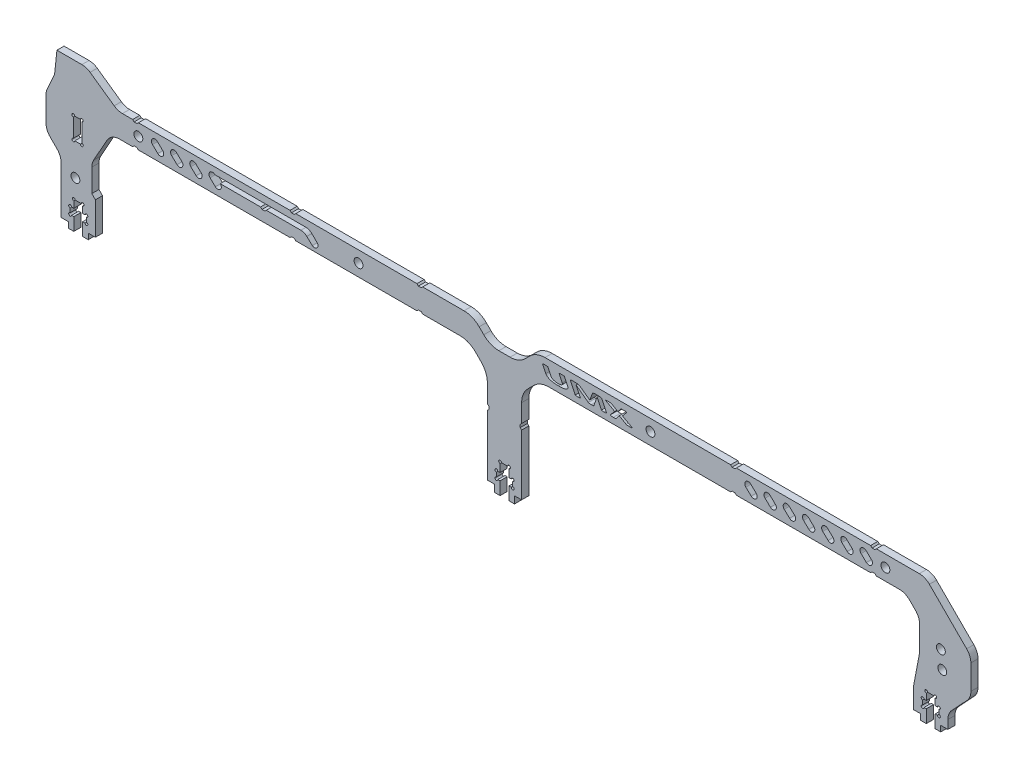
SolidWorks part; units mm, degrees
material "PPS"
ref_plane "前视基准面" through (0, 0, 0) normal (0, 0, 1) x (1, 0, 0)
ref_plane "上视基准面" through (0, 0, 0) normal (0, 1, 0) x (1, 0, 0)
ref_plane "右视基准面" through (0, 0, 0) normal (1, 0, 0) x (0, 0, -1)
sketch "草图1" plane through (0, 0, 0) normal (0, 0, 1) x (1, 0, 0)
  line L0 (-1000, 0) -> (49000, 0) construction
  line L1 (0, 0) -> (0, -218.3822) construction
  line L2 (6, -16.1697) -> (6, -48.75)
  line L3 (6, -48.75) -> (-6, -48.75) construction
  line L4 (-6, -16.1697) -> (-6, -48.75)
  line L5 (6, -48.75) -> (3.5, -48.75)
  line L6 (3.5, -48.75) -> (3.5, -51.25)
  line L7 (3.5, -51.25) -> (-3.5, -51.25) construction
  line L8 (-3.5, -48.75) -> (-3.5, -51.25)
  line L9 (-3.5, -48.75) -> (-6, -48.75)
  line L10 (1.55, -51.25) -> (1.55, -46.75)
  line L11 (1.55, -46.75) -> (2.85, -46.75)
  line L12 (2.85, -46.75) -> (2.85, -44.25)
  line L13 (2.85, -44.25) -> (1.55, -44.25)
  line L14 (1.55, -44.25) -> (1.55, -41)
  line L15 (1.55, -41) -> (-1.55, -41)
  line L16 (-1.55, -44.25) -> (-1.55, -41)
  line L17 (-2.85, -44.25) -> (-1.55, -44.25)
  line L18 (-2.85, -46.75) -> (-2.85, -44.25)
  line L19 (-1.55, -46.75) -> (-2.85, -46.75)
  line L20 (-1.55, -51.25) -> (-1.55, -46.75)
  line L21 (1.55, -51.25) -> (3.5, -51.25)
  line L22 (-1.55, -51.25) -> (-3.5, -51.25)
  line L23 (12.4197, -9.75) -> (6, -16.1697)
  line L24 (-12.4197, -9.75) -> (-6, -16.1697)
  line L25 (-147.7, -45.75) -> (-147.7, -41.25)
  line L26 (-150.8, -45.75) -> (-150.8, -41.25)
  line L27 (-147.7, -41.25) -> (-146.4, -41.25)
  line L28 (-146.4, -41.25) -> (-146.4, -38.75)
  line L29 (-146.4, -38.75) -> (-147.7, -38.75)
  line L30 (-147.7, -38.75) -> (-147.7, -36)
  line L31 (-150.8, -36) -> (-147.7, -36)
  line L32 (-150.8, -38.75) -> (-150.8, -36)
  line L33 (-152.1, -38.75) -> (-150.8, -38.75)
  line L34 (-152.1, -41.25) -> (-152.1, -38.75)
  line L35 (-150.8, -41.25) -> (-152.1, -41.25)
  line L36 (-5.0685, -7.5) -> (5.0685, -7.5)
  line L37 (5.0685, -7.5) -> (11.0685, -1.5)
  line L38 (11.0685, -1.5) -> (147.3211, -1.5)
  line L40 (145.3337, -25.5065) -> (145.3337, -14.709)
  line L41 (140.3747, -9.75) -> (12.4197, -9.75)
  line L42 (-5.0685, -7.5) -> (-11.0685, -1.5)
  line L44 (-11.0685, -1.5) -> (-157.5351, -1.5) construction
  line L45 (-137.7768, -9.75) -> (-12.4197, -9.75)
  line L50 (143.25, -36.4306) -> (143.25, -43.75)
  line L52 (155.25, -43.75) -> (143.25, -43.75) construction
  line L53 (155.25, -43.75) -> (152.75, -43.75)
  line L54 (152.75, -43.75) -> (152.75, -45.75)
  line L55 (152.75, -45.75) -> (145.75, -45.75) construction
  line L56 (145.75, -43.75) -> (145.75, -45.75)
  line L57 (145.75, -43.75) -> (143.25, -43.75)
  line L58 (150.8, -45.75) -> (150.8, -41.25)
  line L59 (150.8, -41.25) -> (152.1, -41.25)
  line L60 (152.1, -41.25) -> (152.1, -38.75)
  line L61 (152.1, -38.75) -> (150.8, -38.75)
  line L62 (150.8, -38.75) -> (150.8, -36)
  line L63 (150.8, -36) -> (147.7, -36)
  line L64 (147.7, -38.75) -> (147.7, -36)
  line L65 (146.4, -38.75) -> (147.7, -38.75)
  line L66 (146.4, -41.25) -> (146.4, -38.75)
  line L67 (147.7, -41.25) -> (146.4, -41.25)
  line L68 (147.7, -45.75) -> (147.7, -41.25)
  line L69 (150.8, -45.75) -> (152.75, -45.75)
  line L70 (147.7, -45.75) -> (145.75, -45.75)
  line L73 (145.3337, -25.5065) -> (143.25, -36.4306)
  line L74 (-147.7, -45.75) -> (-145.75, -45.75)
  line L75 (-150.8, -45.75) -> (-152.75, -45.75)
  line L76 (-152.75, -43.75) -> (-152.75, -45.75)
  line L77 (-155.25, -43.75) -> (-152.75, -43.75)
  line L78 (-145.75, -43.75) -> (-145.75, -45.75)
  line L79 (-145.75, -43.75) -> (-143.25, -43.75)
  line L80 (-157.5351, -1.5) -> (-160.547, -8.1912)
  line L81 (-160.547, -8.1912) -> (-160.547, -19.809)
  line L82 (-160.547, -19.809) -> (-155.25, -25.0873)
  line L87 (-143.25, -32.3726) -> (-144.5, -31.127)
  line L88 (-144.5, -31.127) -> (-144.5, -21.7902)
  line L89 (-144.5, -21.7902) -> (-137.7768, -9.75)
  line L90 (-155.25, -25.0873) -> (-155.25, -43.75)
  line L91 (-143.25, -32.3726) -> (-143.25, -43.75)
  line L92 (147.3211, -1.5) -> (163.2977, -17.4767)
  line L93 (163.2977, -17.4767) -> (163.2977, -30.1638)
  line L94 (163.2977, -30.1638) -> (155.25, -38.75)
  line L95 (155.25, -38.75) -> (155.25, -43.75)
  line L96 (-157.5351, -1.5) -> (-156.7241, 6.25)
  line L97 (-156.7241, 6.25) -> (-146.4, 6.25)
  line L98 (-146.4, 6.25) -> (-135.37, -1.5)
  line L99 (-135.37, -1.5) -> (-11.0685, -1.5)
  line L100 (44.6221, -11.255) -> (57.6009, -11.255) construction
  line L102 (140.3747, -9.75) -> (145.3337, -14.709)
  line L103 (44.6221, -1.505) -> (57.6009, -1.505) construction
  line L104 (146.1658, -18.25) -> (92.972, -18.25) construction
  line L105 (-154.7028, -11.25) -> (-130.7962, -11.25) construction
  circle A0 centre (-51.1115, -5.5) radius 1.55
  circle A1 centre (51.1115, -5.5) radius 1.55
  circle A2 centre (-51.1115, -5.5) radius 1.55 construction
  circle A7 centre (51.1115, -5.5) radius 1.55 construction
  point P6 (0, -48.75)
  point P11 (0, -51.25)
  point P20 (0, -41)
  point P29 (-149.25, -36)
  point P43 (152.75, -44.75)
  point P78 (149.25, -36)
  point P98 (0, 0)
  point P108 (0, 0)
  dimension "D21" = 3.1
  dimension "D1" = 3.5
  dimension "D2" = 4.5
  dimension "D3" = 2.5
  dimension "D4" = 6
  dimension "D5" = 135
  dimension "D6" = 2.5
  dimension "D7" = 48.75
  dimension "D8" = 25.5
  dimension "D9" = 2
  dimension "D10" = 7
  dimension "D11" = 149.25
  dimension "D12" = 1.95
  dimension "D13" = 1.55
  dimension "D14" = 2.85
  dimension "D15" = 10.25
  dimension "D16" = 1.505
  dimension "D17" = 2.25
  dimension "D18" = 135
  dimension "D19" = 135
  dimension "D20" = 1.25
  dimension "D22" = 17.5
  dimension "D23" = 0.005
extrude "凸台-拉伸1" add sketch "草图1" along normal blind 2.5
sketch "草图2" plane through (0, 0, 0) normal (0, 0, 1) x (1, 0, 0)
  line L0 (98.8244, -4.7341) -> (98.8244, -1.5) construction
  line L2 (147.3211, -1.5) -> (11.0685, -1.5) construction
  line L4 (100.6889, -6.5159) -> (100.6889, -9.75) construction
  line L7 (12.4197, -9.75) -> (140.3747, -9.75) construction
  line L8 (94.8107, -5.6378) -> (97.9607, -5.6378) construction
  line L11 (86.3905, -7.4197) -> (84.526, -5.6378)
  line L16 (121.7047, -5.6122) -> (124.8547, -5.6122) construction
  line L17 (106.5671, -7.394) -> (104.7026, -5.6122)
  line L18 (104.7026, -5.6122) -> (106.4054, -3.8303) construction
  line L19 (106.4054, -3.8303) -> (108.27, -5.6122)
  line L20 (108.27, -5.6122) -> (106.5671, -7.394) construction
  line L21 (99.8252, -7.4197) -> (97.9607, -5.6378)
  line L22 (99.6881, -3.8303) -> (101.5526, -5.6122)
  line L23 (101.5526, -5.6122) -> (104.7026, -5.6122) construction
  line L24 (108.27, -5.6122) -> (111.42, -5.6122) construction
  line L25 (113.2845, -7.394) -> (111.42, -5.6122)
  line L26 (113.1228, -3.8303) -> (114.9873, -5.6122)
  line L27 (114.9873, -5.6122) -> (118.1373, -5.6122) construction
  line L28 (120.0018, -7.394) -> (118.1373, -5.6122)
  line L29 (119.8402, -3.8303) -> (121.7047, -5.6122)
  line L30 (126.7192, -7.394) -> (124.8547, -5.6122)
  line L31 (126.5819, -3.8048) -> (128.4464, -5.5866)
  line L32 (86.2289, -3.856) -> (88.0934, -5.6378)
  line L33 (88.0934, -5.6378) -> (91.2434, -5.6378) construction
  line L34 (93.1079, -7.4197) -> (91.2434, -5.6378)
  line L35 (92.9462, -3.856) -> (94.8107, -5.6378)
  line L36 (-106.2679, -5.6378) -> (-103.1179, -5.6378) construction
  line L38 (-112.9852, -5.6378) -> (-109.8352, -5.6378) construction
  line L39 (-121.4054, -7.4197) -> (-123.27, -5.6378)
  line L42 (-107.9707, -7.4197) -> (-109.8352, -5.6378)
  line L44 (-108.1324, -3.856) -> (-106.2679, -5.6378)
  line L47 (-101.2387, -7.4197) -> (-103.1032, -5.6378)
  line L48 (-101.4003, -3.856) -> (-99.5358, -5.6378) construction
  line L51 (-101.4003, -3.856) -> (-69.6149, -3.856)
  line L56 (-121.5671, -3.856) -> (-119.7026, -5.6378)
  line L57 (-119.7026, -5.6378) -> (-116.5526, -5.6378) construction
  line L58 (-114.6881, -7.4197) -> (-116.5526, -5.6378)
  line L59 (-114.8498, -3.856) -> (-112.9852, -5.6378)
  line L60 (-71.3031, -5.6378) -> (-99.5358, -5.6378)
  line L66 (-67.5422, -4.6871) -> (-65.6228, -6.5214)
  line L69 (-67.311, -8.3033) -> (-69.2304, -6.469)
  arc A10 (126.5819, -3.8048) -> (124.8547, -5.6122) centre (125.7183, -4.7085) ccw
  arc A11 (128.4464, -5.5866) -> (126.7192, -7.394) centre (127.5828, -6.4903) cw
  arc A12 (106.4054, -3.8303) -> (104.7026, -5.6122) centre (105.554, -4.7213) ccw
  arc A13 (108.27, -5.6122) -> (106.5671, -7.394) centre (107.4185, -6.5031) cw
  arc A14 (99.6881, -3.8303) -> (97.9607, -5.6378) centre (98.8244, -4.7341) ccw
  arc A15 (101.5526, -5.6122) -> (99.8252, -7.4197) centre (100.6889, -6.5159) cw
  arc A16 (113.1228, -3.8303) -> (111.42, -5.6122) centre (112.2714, -4.7213) ccw
  arc A17 (114.9873, -5.6122) -> (113.2845, -7.394) centre (114.1359, -6.5031) cw
  arc A18 (119.8402, -3.8303) -> (118.1373, -5.6122) centre (118.9887, -4.7213) ccw
  arc A19 (121.7047, -5.6122) -> (120.0018, -7.394) centre (120.8532, -6.5031) cw
  arc A20 (86.2289, -3.856) -> (84.526, -5.6378) centre (85.3774, -4.7469) ccw
  arc A21 (88.0934, -5.6378) -> (86.3905, -7.4197) centre (87.242, -6.5287) cw
  arc A22 (92.9462, -3.856) -> (91.2434, -5.6378) centre (92.0948, -4.7469) ccw
  arc A23 (94.8107, -5.6378) -> (93.1079, -7.4197) centre (93.9593, -6.5287) cw
  arc A34 (-121.5671, -3.856) -> (-123.27, -5.6378) centre (-122.4185, -4.7469) ccw
  arc A35 (-119.7026, -5.6378) -> (-121.4054, -7.4197) centre (-120.554, -6.5287) cw
  arc A36 (-114.8498, -3.856) -> (-116.5526, -5.6378) centre (-115.7012, -4.7469) ccw
  arc A37 (-112.9852, -5.6378) -> (-114.6881, -7.4197) centre (-113.8367, -6.5287) cw
  arc A38 (-108.1324, -3.856) -> (-109.8352, -5.6378) centre (-108.9838, -4.7469) ccw
  arc A39 (-106.2679, -5.6378) -> (-107.9707, -7.4197) centre (-107.1193, -6.5287) cw
  arc A40 (-101.4003, -3.856) -> (-103.1032, -5.6378) centre (-102.2518, -4.7469) ccw
  arc A41 (-99.5358, -5.6378) -> (-101.2387, -7.4197) centre (-100.3873, -6.5287) cw
  arc A46 (-71.3031, -5.6378) -> (-69.2304, -6.469) centre (-71.3031, -8.6378) cw
  arc A47 (-65.6228, -6.5214) -> (-67.311, -8.3033) centre (-66.548, -7.3355) cw
  arc A48 (-69.6149, -3.856) -> (-67.5422, -4.6871) centre (-69.6149, -6.856) cw
extrude "减重" cut sketch "草图2" against normal through all from surface starting at face at (-5.419, -33.6883, 2.5)
sketch "草图5" plane through (0, 0, 0) normal (0, 0, 1) x (1, 0, 0)
  line L0 (-123.27, -5.6378) -> (-121.4054, -7.4197) construction
  line L1 (-126.42, -5.6378) -> (-123.27, -5.6378) construction
  line L2 (-126.42, -5.6378) -> (-128.2845, -3.856) construction
  line L3 (-128.1228, -7.4197) -> (-129.9873, -5.6378) construction
  line L4 (-129.1359, -4.7469) -> (-127.2714, -6.5287) construction
  line L5 (132.4479, -4.6957) -> (134.3124, -6.4776) construction
  line L9 (128.4464, -5.5866) -> (131.5964, -5.5866) construction
  line L10 (135.1638, -5.5866) -> (133.2993, -3.8048) construction
  line L11 (133.4609, -7.3685) -> (131.5964, -5.5866) construction
  arc A1 (-126.42, -5.6378) -> (-128.1228, -7.4197) centre (-127.2714, -6.5287) cw construction
  arc A2 (-129.9873, -5.6378) -> (-128.2845, -3.856) centre (-129.1359, -4.7469) cw construction
  arc A7 (135.1638, -5.5866) -> (133.4609, -7.3685) centre (134.3124, -6.4776) cw construction
  arc A8 (131.5964, -5.5866) -> (133.2993, -3.8048) centre (132.4479, -4.6957) cw construction
  circle A9 centre (-128.2036, -5.6378) radius 1.55
  circle A11 centre (133.3801, -5.5866) radius 1.55
  dimension "D1" = 3.1
extrude "光球接口" cut sketch "草图5" along normal through all
sketch "草图3" plane through (0, 0, 2.5) normal (0, 0, 1) x (1, 0, 0)
  text T0 "<b><i>XMU</i></b>" font "Calibri" height 3.95
extrude "切除-拉伸3" cut sketch "草图3" against normal through all
sketch "草图4" plane through (0, 0, 0) normal (0, 0, 1) x (1, 0, 0)
  line L0 (-6, -25.591) -> (-5.5, -26.091)
  line L1 (-6, -16.1697) -> (-6, -48.75) construction
  line L2 (-5.5, -26.091) -> (-5.5, -27.091)
  line L3 (-5.5, -27.091) -> (-6, -27.591)
  line L4 (-6, -27.591) -> (-6, -25.591)
  line L5 (0, 0) -> (0, -67.6388) construction
  line L6 (6, -27.591) -> (6, -25.591)
  line L7 (5.5, -27.091) -> (6, -27.591)
  line L8 (5.5, -26.091) -> (5.5, -27.091)
  line L9 (6, -25.591) -> (5.5, -26.091)
  line L18 (-11.0685, -1.5) -> (-135.37, -1.5) construction
  line L19 (-128.2051, -1.5) -> (-130.2051, -1.5)
  line L20 (-128.7051, -2) -> (-128.2051, -1.5)
  line L21 (-129.7051, -2) -> (-128.7051, -2)
  line L22 (-130.2051, -1.5) -> (-129.7051, -2)
  line L23 (0, 0) -> (-134.5835, 0) construction
  line L36 (-137.7768, -9.75) -> (-12.4197, -9.75) construction
  line L41 (-99.5358, -5.6378) -> (-71.3031, -5.6378) construction
  line L46 (130.2051, -1.5) -> (129.7051, -2)
  line L47 (129.7051, -2) -> (128.7051, -2)
  line L48 (128.7051, -2) -> (128.2051, -1.5)
  line L49 (128.2051, -1.5) -> (130.2051, -1.5)
  line L50 (-135.37, -1.5) -> (-135.37, -9.75) construction
  line L51 (-1135.37, -5.625) -> (48864.63, -5.625) construction
  line L52 (-130.2051, -9.75) -> (-129.7051, -9.25)
  line L53 (-129.7051, -9.25) -> (-128.7051, -9.25)
  line L54 (-128.7051, -9.25) -> (-128.2051, -9.75)
  line L55 (-128.2051, -9.75) -> (-130.2051, -9.75)
  line L64 (-73.0982, -1.5) -> (-75.0982, -1.5)
  line L65 (-73.5982, -2) -> (-73.0982, -1.5)
  line L66 (-74.5982, -2) -> (-73.5982, -2)
  line L67 (-75.0982, -1.5) -> (-74.5982, -2)
  line L68 (-75.0982, -9.75) -> (-74.5982, -9.25)
  line L69 (-74.5982, -9.25) -> (-73.5982, -9.25)
  line L70 (-73.5982, -9.25) -> (-73.0982, -9.75)
  line L71 (-73.0982, -9.75) -> (-75.0982, -9.75)
  line L72 (-28.6523, -1.5) -> (-30.6523, -1.5)
  line L73 (-29.1523, -2) -> (-28.6523, -1.5)
  line L74 (-30.1523, -2) -> (-29.1523, -2)
  line L75 (-30.6523, -1.5) -> (-30.1523, -2)
  line L76 (-30.6523, -9.75) -> (-30.1523, -9.25)
  line L77 (-30.1523, -9.25) -> (-29.1523, -9.25)
  line L78 (-29.1523, -9.25) -> (-28.6523, -9.75)
  line L79 (-28.6523, -9.75) -> (-30.6523, -9.75)
  line L80 (-83.4194, -5.6378) -> (-85.4194, -5.6378)
  line L81 (-83.9194, -6.1378) -> (-83.4194, -5.6378)
  line L82 (-84.9194, -6.1378) -> (-83.9194, -6.1378)
  line L83 (-85.4194, -5.6378) -> (-84.9194, -6.1378)
  line L92 (79.1823, -9.75) -> (81.1823, -9.75)
  line L93 (128.2051, -9.75) -> (130.2051, -9.75)
  line L94 (128.7051, -9.25) -> (128.2051, -9.75)
  line L95 (129.7051, -9.25) -> (128.7051, -9.25)
  line L96 (130.2051, -9.75) -> (129.7051, -9.25)
  line L97 (-151, -10.625) -> (-148, -10.625)
  line L98 (-148, -10.625) -> (-148, -18.125)
  line L99 (-148, -18.125) -> (-151, -18.125)
  line L100 (-151, -18.125) -> (-151, -10.625)
  line L101 (79.6823, -9.25) -> (79.1823, -9.75)
  line L102 (80.6823, -9.25) -> (79.6823, -9.25)
  line L103 (81.1823, -9.75) -> (80.6823, -9.25)
  line L104 (81.1823, -1.5) -> (80.6823, -2)
  line L105 (80.6823, -2) -> (79.6823, -2)
  line L106 (79.6823, -2) -> (79.1948, -1.5)
  line L107 (79.1948, -1.5) -> (81.1823, -1.5)
  line L108 (147.3211, -1.5) -> (11.0685, -1.5) construction
  line L109 (163.2977, -30.1638) -> (163.2977, -17.4767) construction
  line L110 (-144.5, -31.127) -> (-144.5, -21.7902) construction
  line L112 (-155.25, -43.75) -> (-152.75, -43.75) construction
  circle A0 centre (-150.25, -29.25) radius 1.55
  circle A1 centre (152.7976, -20.675) radius 1.55
  circle A2 centre (153.2976, -26.6541) radius 1.55
  point P4 (-6, -26.591)
  point P19 (-85.4194, -5.6378)
  point P49 (-135.37, -5.625)
  dimension "D13" = 3.1
  dimension "D20" = 3.1
  dimension "D1" = 45
  dimension "D2" = 0.5
  dimension "D3" = 1
  dimension "D4" = 45
  dimension "D5" = 0.5
  dimension "D6" = 1
  dimension "D7" = 45
  dimension "D8" = 1
  dimension "D9" = 6
  dimension "D10" = 15.05
  dimension "D11" = 10.0002
  dimension "D12" = 0.5
  dimension "D14" = 5
  dimension "D15" = 7.5
  dimension "D16" = 3
  dimension "D17" = 14.5
  dimension "D18" = 3.5
  dimension "D19" = 5.75
  dimension "D21" = 148
extrude "线槽和设备接口" cut sketch "草图4" along normal through all
fillet "圆角2" radius 5 16 edges at (155.25, -38.75, 1.25) (145.3337, -25.5065, 1.25) (143.25, -36.4306, 1.25) (147.3211, -1.5, 1.25) (163.2977, -30.1638, 1.25) (163.2977, -17.4767, 1.25) (145.3337, -14.709, 1.25) (140.3747, -9.75, 1.25) (-137.7768, -9.75, 1.25) (-144.5, -21.7902, 1.25) (-146.4, 6.25, 1.25) (-155.25, -25.0873, 1.25) (-160.547, -19.809, 1.25) (-160.547, -8.1912, 1.25) (-157.5351, -1.5, 1.25) (-135.37, -1.5, 1.25)
fillet "圆角3" radius 7.5 8 edges at (12.4197, -9.75, 1.25) (6, -16.1697, 1.25) (-6, -16.1697, 1.25) (-12.4197, -9.75, 1.25) (11.0685, -1.5, 1.25) (5.0685, -7.5, 1.25) (-5.0685, -7.5, 1.25) (-11.0685, -1.5, 1.25)
sketch "草图6" plane through (0, 0, 2.5) normal (0, 0, 1) x (1, 0, 0)
  line L0 (0, 0) -> (0, -63.5679) construction
  circle A0 centre (-151, -10.625) radius 0.5
  circle A1 centre (-148, -10.625) radius 0.5
  circle A2 centre (-151, -18.125) radius 0.5
  circle A3 centre (-148, -18.125) radius 0.5
  circle A4 centre (-150.8, -36) radius 0.5
  circle A5 centre (-147.7, -36) radius 0.5
  circle A6 centre (-152.1, -38.75) radius 0.5
  circle A7 centre (-152.1, -41.25) radius 0.5
  circle A8 centre (-146.4, -38.75) radius 0.5
  circle A9 centre (-146.4, -41.25) radius 0.5
  circle A10 centre (-2.85, -44.25) radius 0.5
  circle A11 centre (-2.85, -46.75) radius 0.5
  circle A12 centre (-1.55, -41) radius 0.5
  circle A13 centre (-3.5, -48.75) radius 0.5 construction
  circle A15 centre (-152.75, -43.75) radius 0.5 construction
  circle A16 centre (-145.75, -43.75) radius 0.5 construction
  circle A17 centre (145.75, -43.75) radius 0.5 construction
  circle A18 centre (152.75, -43.75) radius 0.5 construction
  circle A19 centre (3.5, -48.75) radius 0.5 construction
  circle A20 centre (1.55, -41) radius 0.5
  circle A21 centre (2.85, -46.75) radius 0.5
  circle A22 centre (2.85, -44.25) radius 0.5
  circle A23 centre (146.4, -41.25) radius 0.5
  circle A24 centre (146.4, -38.75) radius 0.5
  circle A25 centre (152.1, -41.25) radius 0.5
  circle A26 centre (152.1, -38.75) radius 0.5
  circle A27 centre (147.7, -36) radius 0.5
  circle A28 centre (150.8, -36) radius 0.5
  dimension "D1" = 1
extrude "直角约束" cut sketch "草图6" against normal through all
